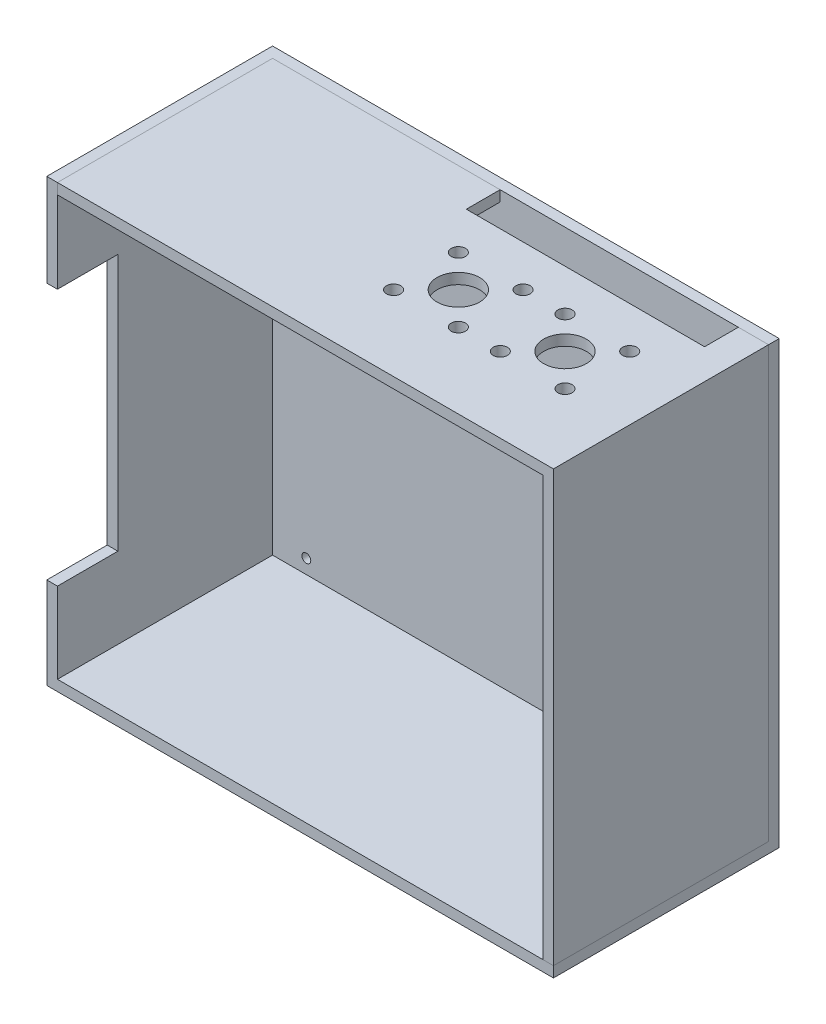
SolidWorks part; units mm, degrees
ref_plane "Alzado" through (0, 0, 0) normal (0, 0, 1) x (1, 0, 0)
ref_plane "Planta" through (0, 0, 0) normal (0, 1, 0) x (1, 0, 0)
ref_plane "Vista lateral" through (0, 0, 0) normal (1, 0, 0) x (0, 0, -1)
sketch "Croquis1" plane through (0, 0, 0) normal (0, 1, 0) x (1, 0, 0)
  line L0 (-68.25, 28.75) -> (68.25, 28.75)
  line L1 (-71.25, -31.75) -> (71.25, -31.75)
  line L2 (-71.25, -31.75) -> (-71.25, 31.75)
  line L3 (-71.25, 31.75) -> (71.25, 31.75)
  line L4 (71.25, -31.75) -> (71.25, 31.75)
  line L5 (-71.25, -31.75) -> (71.25, 31.75) construction
  line L6 (-71.25, 31.75) -> (71.25, -31.75) construction
  line L7 (68.25, -28.75) -> (68.25, 28.75)
  line L8 (-68.25, -28.75) -> (68.25, -28.75)
  line L9 (-68.25, -28.75) -> (-68.25, 28.75)
  line L10 (-68.25, -28.75) -> (-68.25, -31.75)
  line L11 (68.25, 28.75) -> (71.25, 28.75)
  point P0 (0, 0)
  dimension "D1" = 142.5
  dimension "D2" = 63.5
  dimension "D3" = 3
extrude "Saliente-Extruir1" add sketch "Croquis1" along normal blind 124 contours L0 L11 L4 L3 L2 L1 L10 L9 region at (-69.8101, 0, 0)
sketch "Croquis2" plane through (0, 0, 0) normal (0, -1, 0) x (1, 0, 0)
  line L1 (-71.25, 31.75) -> (71.25, 31.75)
  line L2 (-71.25, 31.75) -> (-71.25, -31.75)
  line L3 (-71.25, -31.75) -> (71.25, -31.75)
  line L4 (71.25, 31.75) -> (71.25, -31.75)
extrude "Saliente-Extruir2" add sketch "Croquis2" against normal blind 3
sketch "Croquis3" plane through (-71.25, 0, 0) normal (-1, 0, 0) x (0, 0, 1)
  line L1 (31.75, 124) -> (14.75, 124)
  line L2 (31.75, 124) -> (31.75, 98)
  line L3 (31.75, 98) -> (14.75, 98)
  line L4 (-31.75, 0) -> (31.75, 0)
  line L5 (31.75, 0) -> (31.75, 124)
  line L6 (31.75, 124) -> (-31.75, 124)
  line L7 (-31.75, 124) -> (-31.75, 0)
  line L8 (-31.75, 0) -> (31.75, 0)
  line L9 (31.75, 0) -> (31.75, 124)
  line L10 (31.75, 124) -> (-31.75, 124)
  line L11 (-31.75, 124) -> (-31.75, 0)
  line L12 (14.75, 124) -> (14.75, 98)
  line L13 (14.75, 98) -> (31.75, 98)
  line L14 (14.75, 98) -> (14.75, 25.7)
  line L15 (14.75, 25.7) -> (31.75, 25.7)
  line L16 (31.75, 98) -> (31.75, 25.7)
  dimension "D2" = 26
  dimension "D3" = 17
  dimension "D4" = 72.3
  dimension "D1" = 0
extrude "Cortar-Extruir1" cut sketch "Croquis3" against normal blind 3 contours L14 L15 L9 L3 region at (-71.25, 61.85, 23.25)
sketch "Croquis4" plane through (0, 124, 0) normal (0, 1, 0) x (1, 0, 0)
  line L1 (-68.25, -31.75) -> (71.25, -31.75)
  line L2 (-68.25, -31.75) -> (-68.25, 28.75)
  line L3 (-68.25, 28.75) -> (71.25, 28.75)
  line L4 (71.25, -31.75) -> (71.25, 28.75)
  line L6 (-68.25, 28.75) -> (71.25, 28.75)
  line L7 (71.25, 28.75) -> (71.25, 31.75)
  line L8 (71.25, 31.75) -> (-71.25, 31.75)
  line L9 (-71.25, 31.75) -> (-71.25, -31.75)
  line L10 (-71.25, -31.75) -> (-68.25, -31.75)
  line L11 (-68.25, -31.75) -> (-68.25, 28.75)
  line L12 (-68.25, 28.75) -> (71.25, 28.75)
  line L13 (71.25, 28.75) -> (71.25, 31.75)
  line L14 (71.25, 31.75) -> (-71.25, 31.75)
  line L15 (-71.25, 31.75) -> (-71.25, -31.75)
  line L16 (-71.25, -31.75) -> (-68.25, -31.75)
  line L17 (-68.25, -31.75) -> (-68.25, 28.75)
  line M7 (-68.25, 28.75) -> (71.25, 28.75)
  line M12 (-68.25, -31.75) -> (-68.25, 28.75)
  dimension "D1" = 0
extrude "Saliente-Extruir4" add sketch "Croquis4" against normal blind 3 separate body contours L1 L4 M7 M12 region at (1.5, 124, 1.5)
sketch "Croquis5" plane through (71.25, 0, 0) normal (1, 0, 0) x (0, 0, -1)
  line L1 (-31.75, 121) -> (28.75, 121)
  line L2 (-31.75, 121) -> (-31.75, 3)
  line L3 (-31.75, 3) -> (28.75, 3)
  line L4 (28.75, 124) -> (-31.75, 124)
  line L5 (-31.75, 124) -> (-31.75, 121)
  line L6 (-31.75, 121) -> (28.75, 121)
  line L7 (28.75, 121) -> (28.75, 124)
  line L8 (28.75, 124) -> (-31.75, 124)
  line L9 (-31.75, 124) -> (-31.75, 121)
  line L10 (-31.75, 121) -> (28.75, 121)
  line L11 (28.75, 121) -> (28.75, 124)
  line L12 (28.75, 121) -> (28.75, 3)
  line M7 (-31.75, 121) -> (28.75, 121)
  dimension "D1" = 0
extrude "Saliente-Extruir5" add sketch "Croquis5" against normal blind 3 separate body contours L12 L2 L3 M7 region at (71.25, 62, 1.5)
sketch "Croquis6" plane through (0, 0, -31.75) normal (0, 0, -1) x (-1, 0, 0)
  line L1 (-71.25, 124) -> (-58.75, 124)
  line L2 (-71.25, 124) -> (-71.25, 117)
  line L3 (-71.25, 117) -> (-58.75, 117)
  line L4 (-58.75, 124) -> (-58.75, 117)
  line L5 (71.25, 124) -> (58.75, 124)
  line L6 (71.25, 124) -> (71.25, 117)
  line L7 (71.25, 117) -> (58.75, 117)
  line L8 (58.75, 124) -> (58.75, 117)
  circle A0 centre (-58.75, 117) radius 1.25
  circle A1 centre (58.75, 117) radius 1.25
  dimension "D3" = 2.5
  dimension "D6" = 2.5
  dimension "D1" = 7
  dimension "D2" = 12.5
  dimension "D4" = 12.5
  dimension "D5" = 7
extrude "Cortar-Extruir2" cut sketch "Croquis6" against normal blind 3 contours A1 | A0
sketch "Croquis7" plane through (0, 124, 0) normal (0, 1, 0) x (1, 0, 0)
  line L0 (-68.25, 28.75) -> (71.25, 28.75) construction
  line L1 (-71.25, 31.75) -> (-4.25, 31.75)
  line L2 (-71.25, 31.75) -> (-71.25, 19.25)
  line L3 (-71.25, 19.25) -> (-4.25, 19.25)
  line L4 (-4.25, 31.75) -> (-4.25, 19.25)
  line L5 (-4.25, 19.25) -> (62.75, 19.25)
  line L6 (-4.25, 19.25) -> (-4.25, 28.75)
  line L7 (-4.25, 28.75) -> (62.75, 28.75)
  line L8 (62.75, 19.25) -> (62.75, 28.75)
  line M4 (-68.25, 28.75) -> (71.25, 28.75)
  dimension "D1" = 67
  dimension "D2" = 12.5
  dimension "D3" = 67
extrude "Cortar-Extruir3" cut sketch "Croquis7" against normal blind 3 contours L5 L8 L4 M4 region at (29.25, 124, -24)
sketch "Croquis9" plane through (0, 0, -31.75) normal (0, 0, -1) x (-1, 0, 0)
  line L0 (-71.25, 62) -> (71.25, 62)
  line L1 (71.25, 62) -> (0, 62)
  line L3 (-58.75, 7) -> (58.75, 7)
  line L4 (-71.25, 0) -> (71.25, 0)
  line L5 (71.25, 0) -> (71.25, 124)
  line L6 (71.25, 124) -> (-71.25, 124)
  line L7 (-71.25, 124) -> (-71.25, 0)
  line L8 (-71.25, 0) -> (71.25, 0)
  line L9 (71.25, 0) -> (71.25, 124)
  line L10 (71.25, 124) -> (-71.25, 124)
  line L11 (-71.25, 124) -> (-71.25, 0)
  line L12 (-58.75, 7) -> (-58.75, 117)
  line L13 (-58.75, 117) -> (58.75, 117)
  line L14 (58.75, 7) -> (58.75, 117)
  line L15 (-58.75, 7) -> (58.75, 117) construction
  line L16 (-58.75, 117) -> (58.75, 7) construction
  circle A0 centre (58.75, 7) radius 1.25
  circle A1 centre (-58.75, 7) radius 1.25
  dimension "D2" = 2.5
  dimension "D3" = 2.5
  dimension "D1" = 0
extrude "Cortar-Extruir6" cut sketch "Croquis9" against normal blind 3 contours A1 | A0
combine bodies "Combinar1" operation type add bodies to combine 106 108
sketch "Croquis10" plane through (0, 124, 0) normal (0, 1, 0) x (1, 0, 0)
  line L0 (35.15, 7.6) -> (53.35, 7.6) construction
  line L1 (5.15, 7.6) -> (23.35, 7.6) construction
  line L2 (5.15, 7.6) -> (5.15, -10.6) construction
  line L3 (5.15, -10.6) -> (23.35, -10.6) construction
  line L4 (23.35, 7.6) -> (23.35, -10.6) construction
  line L5 (5.15, 7.6) -> (23.35, -10.6) construction
  line L6 (5.15, -10.6) -> (23.35, 7.6) construction
  line L7 (35.15, 7.6) -> (35.15, -10.6) construction
  line L8 (35.15, -10.6) -> (53.35, -10.6) construction
  line L9 (53.35, 7.6) -> (53.35, -10.6) construction
  line L10 (35.15, 7.6) -> (53.35, -10.6) construction
  line L11 (35.15, -10.6) -> (53.35, 7.6) construction
  line L13 (14.25, -1.5) -> (44.25, -1.5) construction
  line L14 (-4.25, 19.25) -> (62.75, 19.25) construction
  line L15 (71.25, -31.75) -> (71.25, 28.75) construction
  circle A0 centre (14.25, -1.5) radius 6
  circle A1 centre (23.35, 7.6) radius 2
  circle A2 centre (5.15, 7.6) radius 2
  circle A3 centre (5.15, -10.6) radius 2
  circle A4 centre (23.35, -10.6) radius 2
  circle A5 centre (44.25, -1.5) radius 6
  circle A6 centre (53.35, 7.6) radius 2
  circle A7 centre (35.15, 7.6) radius 2
  circle A8 centre (35.15, -10.6) radius 2
  circle A9 centre (53.35, -10.6) radius 2
  point P22 (29.25, 19.25)
  point P23 (29.25, -1.5)
  point P28 (71.25, -1.5)
  dimension "D1" = 12
  dimension "D3" = 4
  dimension "D4" = 12
  dimension "D6" = 4
  dimension "D2" = 18.2
  dimension "D5" = 18.2
  dimension "D7" = 30
extrude "Cortar-Extruir7" cut sketch "Croquis10" against normal blind 10
